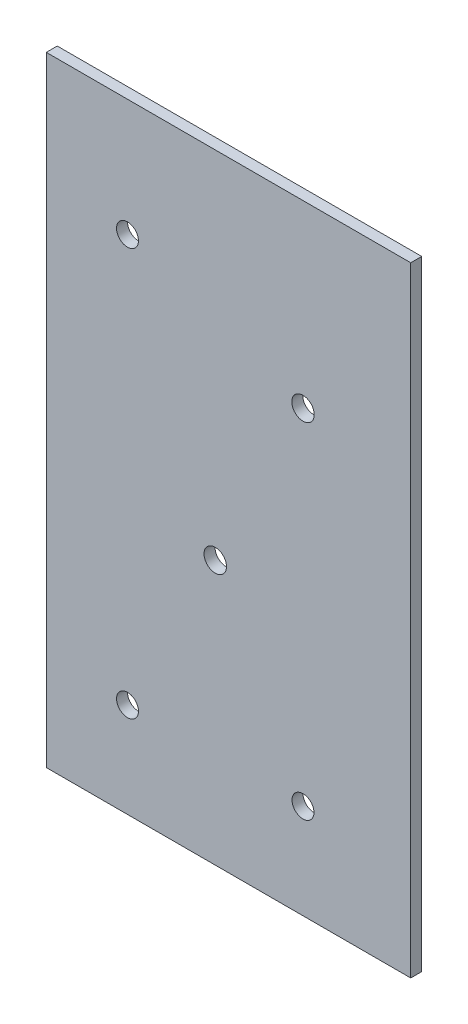
SolidWorks part; units mm, degrees
ref_plane "Front Plane" through (0, 0, 0) normal (0, 0, 1) x (1, 0, 0)
ref_plane "Top Plane" through (0, 0, 0) normal (0, 1, 0) x (1, 0, 0)
ref_plane "Right Plane" through (0, 0, 0) normal (1, 0, 0) x (0, 0, -1)
sketch "Sketch1" plane through (0, 0, 0) normal (0, 0, 1) x (1, 0, 0)
  line L0 (88.9, 95.25) -> (63.5, 95.25) construction
  line L1 (1.8891, 210.8161) -> (107.3869, 210.8161)
  line L2 (1.8891, 210.8161) -> (1.8891, 31.5173)
  line L3 (1.8891, 31.5173) -> (107.3869, 31.5173)
  line L4 (107.3869, 210.8161) -> (107.3869, 31.5173)
  line L5 (63.5, 95.25) -> (63.5, 146.05) construction
  line L8 (88.9, 95.25) -> (88.9, 146.05) construction
  circle A0 centre (25.4, 58.9643) radius 3.175
  circle A1 centre (76.2, 58.9643) radius 3.175
  circle A2 centre (25.4, 176.8929) radius 3.175
  circle A4 centre (76.2, 158.75) radius 3.2512
  circle A6 centre (50.8, 107.95) radius 3.2512
  dimension "D1" = 6.35
  dimension "D6" = 6.5024
  dimension "D4" = 12.7
  dimension "D7" = 33.9233
  dimension "D8" = 23.5109
  dimension "D9" = 27.447
  dimension "D10" = 31.1869
  dimension "D5" = 12.7
  dimension "D2" = 12.7
  dimension "D3" = 12.7
extrude "Boss-Extrude1" add sketch "Sketch1" along normal blind 3.175
equation "\"80/20 to Center Hole\"= .64in"
equation "\"80/20 from Edge\"= 0.5in"
equation "\"D5@Sketch1\"=\"80/20 from Edge\""
equation "\"D3@Sketch1\"=\"80/20 from Edge\""
